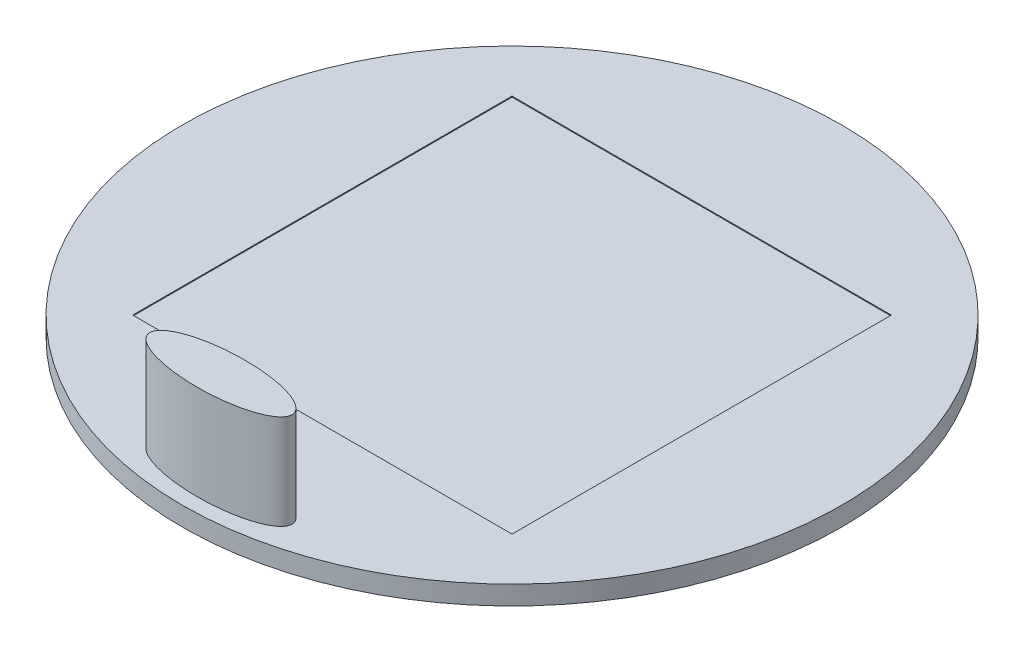
SolidWorks part; units mm, degrees
ref_plane "Front Plane" through (0, 0, 0) normal (0, 0, 1) x (1, 0, 0)
ref_plane "Top Plane" through (0, 0, 0) normal (0, 1, 0) x (1, 0, 0)
ref_plane "Right Plane" through (0, 0, 0) normal (1, 0, 0) x (0, 0, -1)
sketch "Sketch1" plane through (0, 0, 0) normal (0, 1, 0) x (1, 0, 0)
  line L0 (-2.5, -2) -> (2.5, -2) construction
  line L1 (2.5, -2) -> (0, 5) construction
  line L2 (0, 5) -> (-2.5, -2) construction
  line L3 (0, 0) -> (0, -2) construction
  line L4 (0, 5.5946) -> (-2.7838, -2.2)
  line L5 (-2.7838, -2.2) -> (2.7838, -2.2)
  line L6 (2.7838, -2.2) -> (0, 5.5946)
  line L7 (-33.1075, 10.5571) -> (-33.1075, -10.5571)
  circle A0 centre (0, 0) radius 35 construction
  circle A1 centre (0, 0) radius 34.75
  dimension "D1" = 70
  dimension "D3" = 7
  dimension "D4" = 5
  dimension "D5" = 2
  dimension "D2" = 0.25
  dimension "D6" = 0.2
extrude "Boss-Extrude1" add sketch "Sketch1" along normal blind 2 contours L5 L6 L4 | A1 L6 L5 L4 | L7 A1 region at (0, 0, -0.3982) region at (5.1927, 0, -33.3771) region at (-33.7659, 0, 0)
extrude "Cut-Extrude1" cut sketch "Sketch1<4>" along normal blind 1 contours L5 L6 L4 region at (0, 0, -0.3982)
sketch "Sketch1<4>" plane through (0, 0, 0) normal (0, 1, 0) x (1, 0, 0) same geometry as "Sketch1"
extrude "Cut-Extrude2" cut sketch "Sketch1<5>" along normal blind 1 contours L7 A1 region at (-33.7659, 0, 0)
sketch "Sketch1<5>" plane through (0, 0, 0) normal (0, 1, 0) x (1, 0, 0) same geometry as "Sketch1"
sketch "Sketch3" plane through (0, 2, 0) normal (0, 1, 0) x (1, 0, 0)
  line L0 (-7.5, -30.6947) -> (7.5, -30.6947) construction
  ellipse E0 centre (0, -30.6947) end of major axis (7.5, -30.6947) minor radius 2.5
  dimension "D1" = 5
  dimension "D2" = 15
extrude "Boss-Extrude2" add sketch "Sketch3" along normal blind 10
sketch "Sketch4" plane through (0, 2, 0) normal (0, 1, 0) x (1, 0, 0)
  line L1 (-20, 20) -> (20, 20)
  line L2 (-20, 20) -> (-20, -20)
  line L3 (-20, -20) -> (20, -20)
  line L4 (20, 20) -> (20, -20)
  line L5 (-20, 20) -> (20, -20) construction
  line L6 (-20, -20) -> (20, 20) construction
  point P0 (0, 0)
  dimension "D1" = 40
extrude "Cut-Extrude3" cut sketch "Sketch4" against normal blind 0.1
